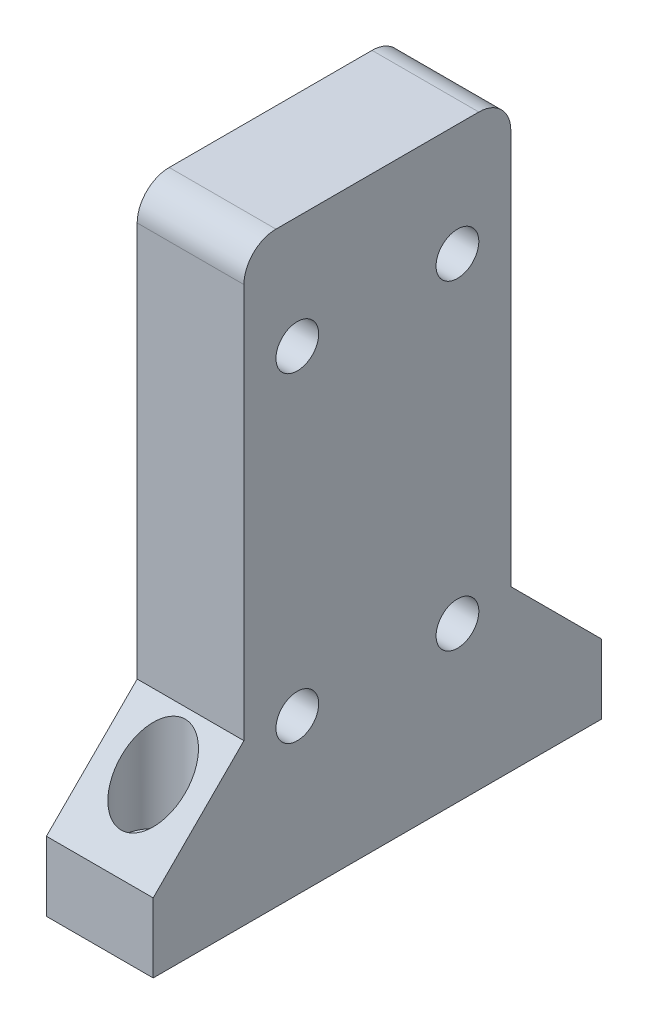
SolidWorks part; units mm, degrees
ref_plane "Front Plane" through (0, 0, 0) normal (0, 0, 1) x (1, 0, 0)
ref_plane "Top Plane" through (0, 0, 0) normal (0, 1, 0) x (1, 0, 0)
ref_plane "Right Plane" through (0, 0, 0) normal (1, 0, 0) x (0, 0, -1)
sketch "Sketch1" plane through (0, 0, 0) normal (0, 1, 0) x (1, 0, 0)
  line L0 (0, 16) -> (0, -16) construction
  line L1 (-5, 21) -> (5, 21)
  line L7 (-5, 21) -> (-5, -21)
  line L8 (-5, -21) -> (5, -21)
  line L13 (5, 21) -> (5, -21)
  line L14 (-5, 21) -> (5, -21) construction
  line L18 (-5, -21) -> (5, 21) construction
  circle A4 centre (0, 16) radius 1.6 construction
  circle A5 centre (0, -16) radius 1.6 construction
  point P0 (0, 0)
  dimension "D1" = 3.2
  dimension "D2" = 3.2
  dimension "D3" = 32
  dimension "D4" = 5
  dimension "D5" = 5
extrude "Boss-Extrude1" add sketch "Sketch1" along normal blind 3
sketch "Sketch7" plane through (0, 3, 0) normal (0, 1, 0) x (1, 0, 0)
  line L0 (5, -21) -> (5, 21) construction
  line L1 (-5, 12.5) -> (5, 12.5)
  line L2 (-5, 12.5) -> (-5, -12.5)
  line L3 (-5, -12.5) -> (5, -12.5)
  line L4 (5, 12.5) -> (5, -12.5)
  line L5 (-5, 12.5) -> (5, -12.5) construction
  line L6 (-5, -12.5) -> (5, 12.5) construction
  point P0 (0, 0)
  dimension "D1" = 25
extrude "Boss-Extrude4" add sketch "Sketch7" along normal blind 52
chamfer "Chamfer2" distance 12 angle 45 2 edges at (0, 3, 12.5) (0, 3, -12.5)
sketch "Sketch8" plane through (0, 55, 0) normal (0, 1, 0) x (1, 0, 0)
  line L0 (0, 16) -> (0, -16) construction
  circle A0 centre (0, 16) radius 1.75
  circle A1 centre (0, -16) radius 1.75
  dimension "D2" = 3.5
  dimension "D3" = 3.5
  dimension "D1" = 32
extrude "Cut-Extrude1" cut sketch "Sketch8" against normal through all
sketch "Sketch9" plane through (0, 55, 0) normal (0, 1, 0) x (1, 0, 0)
  circle A0 centre (0, 16) radius 3
  circle A1 centre (0, -16) radius 3
  dimension "D1" = 6
  dimension "D2" = 6
extrude "Cut-Extrude2" cut sketch "Sketch9" against normal offset from surface (50 mm away) 5 up to face at (0, 0, -14.25)
sketch "Sketch10" plane through (-5, 0, 0) normal (-1, 0, 0) x (0, 0, 1)
  line L0 (-7.5, 55) -> (-7.5, 0) construction
  line L1 (-12.5, 55) -> (12.5, 55) construction
  line L2 (-21, 0) -> (21, 0) construction
  line L3 (7.5, 55) -> (7.5, 0) construction
  line L4 (-7.5, 55) -> (7.5, 55) construction
  line L5 (-7.5, 44.5) -> (7.5, 44.5) construction
  line L6 (-7.5, 14.5) -> (7.5, 14.5) construction
  circle A0 centre (-7.5, 14.5) radius 2
  circle A1 centre (7.5, 14.5) radius 2
  circle A2 centre (-7.5, 44.5) radius 2
  circle A3 centre (7.5, 44.5) radius 2
  point P8 (0, 55)
  dimension "D1" = 4
  dimension "D2" = 4
  dimension "D3" = 4
  dimension "D4" = 4
  dimension "D5" = 15
  dimension "D6" = 10.5
  dimension "D7" = 30
fillet "Fillet1" radius 3 2 edges at (0, 55, 12.5) (0, 55, -12.5)
extrude "Cut-Extrude3" cut sketch "Sketch10" against normal through all
